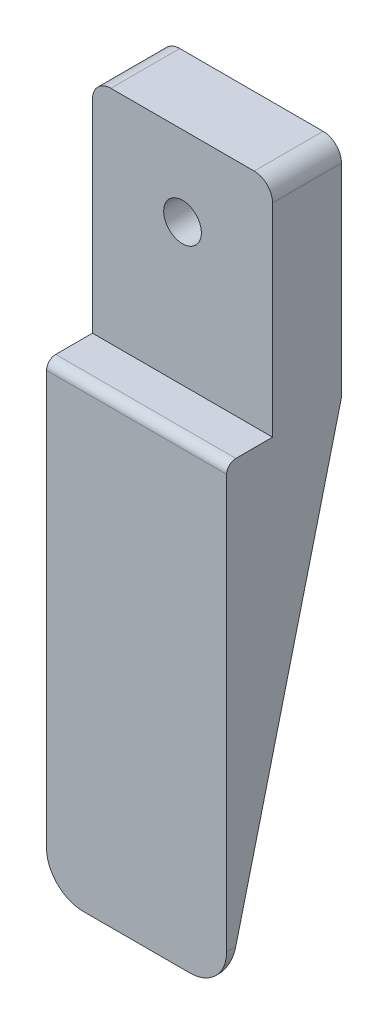
SolidWorks part; units mm, degrees
ref_plane "Front Plane" through (0, 0, 0) normal (0, 0, 1) x (1, 0, 0)
ref_plane "Top Plane" through (0, 0, 0) normal (0, 1, 0) x (1, 0, 0)
ref_plane "Right Plane" through (0, 0, 0) normal (1, 0, 0) x (0, 0, -1)
sketch "Sketch1" plane through (0, 0, 0) normal (0, 0, 1) x (1, 0, 0)
  line L0 (9.8, -43) -> (-9.8, -43)
  line L3 (-9.8, -43) -> (-9.8, -67.081)
  line L4 (-15, -67.081) -> (15, -67.081) construction
  line L5 (-9.8, -67.081) -> (9.8, -67.081)
  line L6 (9.8, -67.081) -> (9.8, -43)
  line L7 (10, -38.7298) -> (10, -62.2236) construction
  line L8 (-10, -62.2236) -> (-10, -38.7298) construction
  line L9 (-9.8, -67.081) -> (-9.8, -113.081)
  line L10 (-5.8, -117.081) -> (5.8, -117.081)
  line L11 (9.8, -113.081) -> (9.8, -67.081)
  arc A0 (-10, -41.821) -> (10, -41.821) centre (0, 0) ccw construction
  arc A1 (5.8, -117.081) -> (9.8, -113.081) centre (5.8, -113.081) ccw
  arc A2 (-9.8, -113.081) -> (-5.8, -117.081) centre (-5.8, -113.081) ccw
  point P19 (-9.8, -117.081)
  dimension "D4" = 4
  dimension "D1" = 0.2
  dimension "D2" = 0.2
  dimension "D3" = 50
extrude "Boss-Extrude1" add sketch "Sketch1" against normal blind 12.5 contours L10 L11 L5 L9 | L5 L6 L0 L3 region at (0, -55.0405, 0) region at (0, -91.9109, 0)
sketch "Sketch2" plane through (9.8, 0, 0) normal (1, 0, 0) x (0, 0, -1)
  line L0 (0, -43) -> (5, -43)
  line L2 (5, -43) -> (5, -67.081)
  line L3 (5, -67.081) -> (0, -67.081) construction
  line L4 (0, -113.081) -> (0, -43) construction
  line L5 (5, -67.081) -> (0, -67.081) construction
  line L6 (12.5, -67.081) -> (0, -117.081)
  line L7 (12.5, -113.081) -> (12.5, -43) construction
  line L8 (12.5, -117.081) -> (0, -117.081) construction
  line L9 (12.5, -67.081) -> (12.5, -117.081)
  line L10 (12.5, -117.081) -> (0, -117.081)
  line L11 (5, -41.821) -> (5, -64.2376) construction
  line L12 (5, -67.281) -> (0, -67.281)
  line L13 (5, -67.081) -> (5, -67.281)
  line L14 (0, -67.281) -> (0, -67.081)
  line M6 (0, -43) -> (0, -113.081)
  line M8 (12.5, -113.081) -> (12.5, -43)
  line M9 (12.5, -43) -> (0, -43)
  line M20 (0, -113.081) -> (12.5, -113.081)
  dimension "D1" = 0.2
extrude "Cut-Extrude1" cut sketch "Sketch2" against normal up to next contours L3 L2 M9 M6 | L6 M8 | L10 L9 L6 M20 region at (9.8, -55.0405, -2.5) region at (9.8, -97.7477, -8.6667) region at (9.8, -115.1088, -6.4965)
sketch "Sketch3" plane through (0, 0, -12.5) normal (0, 0, -1) x (-1, 0, 0)
  circle A0 centre (0, -51.7024) radius 2.05 construction
  circle A1 centre (0, -51.7024) radius 2.05
extrude "Cut-Extrude2" cut sketch "Sketch3" against normal up to next
fillet "Fillet1" radius 2 2 edges at (9.8, -43, -8.75) (-9.8, -43, -8.75)
fillet "Fillet2" radius 1 1 edges at (0, -67.081, 0)
sketch "Sketch4" plane through (0, 0, -12.5) normal (0, 0, -1) x (-1, 0, 0)
  circle A0 centre (0, -51.7024) radius 4.15
  dimension "D1" = 8.3
extrude "Cut-Extrude3" cut sketch "Sketch4" against normal blind 2.5
chamfer "Chamfer1" distance 0.5 angle 45 2 edges at (-2.05, -51.7024, -10) (-4.15, -51.7024, -12.5)
